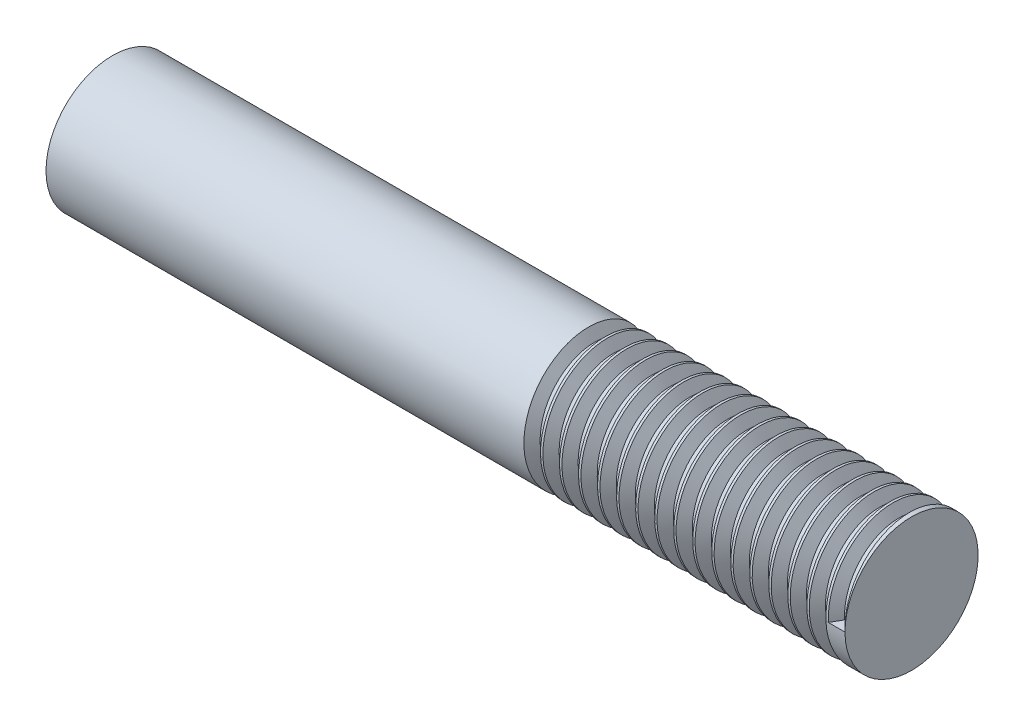
SolidWorks part; units mm, degrees
ref_plane "Front Plane" through (0, 0, 0) normal (0, 0, 1) x (1, 0, 0)
ref_plane "Top Plane" through (0, 0, 0) normal (0, 1, 0) x (1, 0, 0)
ref_plane "Right Plane" through (0, 0, 0) normal (1, 0, 0) x (0, 0, -1)
sketch "Sketch1" plane through (0, 0, 0) normal (1, 0, 0) x (0, 0, -1)
  circle A0 centre (0, 0) radius 3.175
  dimension "D1" = 6.35
extrude "Boss-Extrude1" add sketch "Sketch1" along normal blind 38.1
thread "Thread1" pitch 0.9071 method cut profile "Thread Profile1" start angle 0, offset 0, length 15.24, pitch 0.9071, diameter 6.35
ref_plane "Plane1" through (38.1, 0, 3.175) normal (0, -1, 0) x (0, 0, 1)
sketch "Thread Profile1" plane through (38.1, 0, 3.175) normal (0, -1, 0) x (0, 0, 1)
  line L0 (0, 0) -> (0, 0.9071) construction
  line L11 (0, 0) -> (0, 0.7937)
  line L12 (0, 0.7937) -> (-0.491, 0.5103)
  line L13 (-0.491, 0.5103) -> (-0.491, 0.2835)
  line L15 (-0.491, 0.2835) -> (0, 0)
  line L17 (-0.491, 0.3969) -> (0, 0.3969) construction
  point P2 (0, 0)
  dimension "Pitch" = 0.9071
  dimension "Profile_Angle" = 60
  dimension "Profile_Land" = 0.2268
  dimension "Profile_Height" = 0.491
